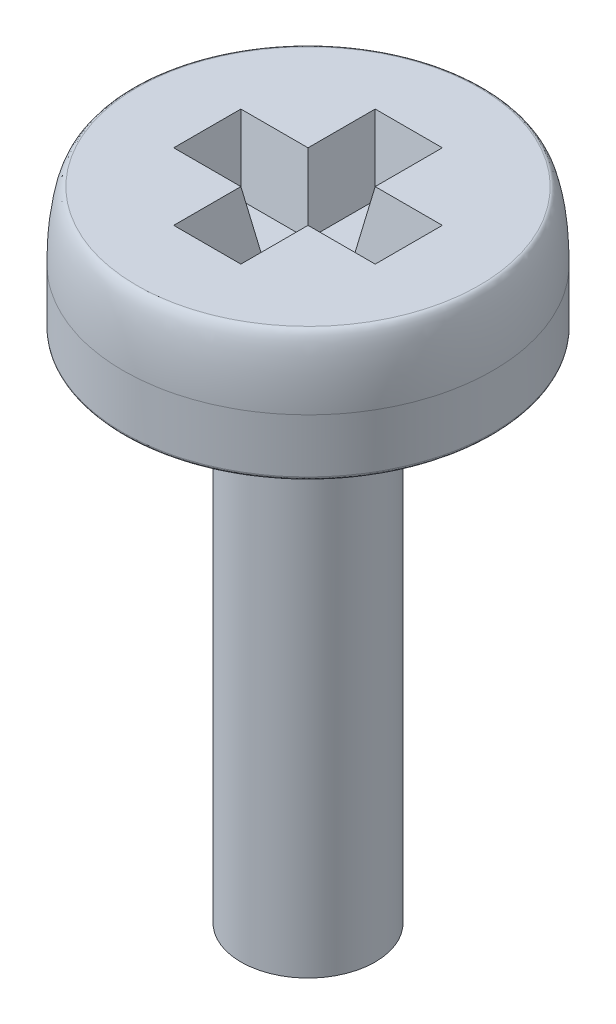
SolidWorks part; units mm, degrees
ref_plane "Front Plane" through (0, 0, 0) normal (0, 0, 1) x (1, 0, 0)
ref_plane "Top Plane" through (0, 0, 0) normal (0, 1, 0) x (1, 0, 0)
ref_plane "Right Plane" through (0, 0, 0) normal (1, 0, 0) x (0, 0, -1)
sketch "Sketch1" plane through (0, 0, 0) normal (0, 1, 0) x (1, 0, 0)
  circle A0 centre (0, 0) radius 2.75
  dimension "D1" = 5.5
extrude "Boss-Extrude1" add sketch "Sketch1" along normal blind 2
fillet "Fillet1" radius 1 2 edges at (0, 2, 2.75) (0, 0, 2.75) second distance 0.2 first distance on face at (0, 2, 2.75) first distance on face at (0, 0, 2.75)
sketch "Sketch2" plane through (0, 0, 0) normal (0, -1, 0) x (1, 0, 0)
  circle A0 centre (0, 0) radius 1
  dimension "D1" = 2
extrude "Boss-Extrude2" add sketch "Sketch2" along normal blind 7.5
sketch "Sketch3" plane through (0, -7.5, 0) normal (0, -1, 0) x (1, 0, 0)
  circle A0 centre (0, 0) radius 1.25
  dimension "D1" = 2.5
curve "Helix/Spiral1" pitch 0.9375 height 7.5 turns 8
sketch "Sketch5" plane through (0, 2, 0) normal (0, 1, 0) x (1, 0, 0)
  line L0 (0.5, 0.5) -> (1.5, 0.5)
  line L1 (0.5, 1.5) -> (-0.5, 1.5)
  line L2 (0.5, 1.5) -> (0.5, 0.5)
  line L3 (0.5, -1.5) -> (-0.5, -1.5)
  line L4 (-0.5, 1.5) -> (-0.5, 0.5)
  line L5 (-1.5, 0.5) -> (-0.5, 0.5)
  line L6 (-1.5, 0.5) -> (-1.5, -0.5)
  line L7 (-1.5, -0.5) -> (-0.5, -0.5)
  line L8 (1.5, 0.5) -> (1.5, -0.5)
  line L9 (0.5, -0.5) -> (0.5, -1.5)
  line L10 (0.5, -0.5) -> (1.5, -0.5)
  line L11 (-0.5, -0.5) -> (-0.5, -1.5)
  dimension "D1" = 1
  dimension "D2" = 3
  dimension "D3" = 1
  dimension "D4" = 3
  dimension "D5" = 1.5
  dimension "D6" = 0.5
  dimension "D7" = 1.5
  dimension "D8" = 0.5
extrude "Cut-Extrude1" cut sketch "Sketch5" against normal blind 1 draft 10
